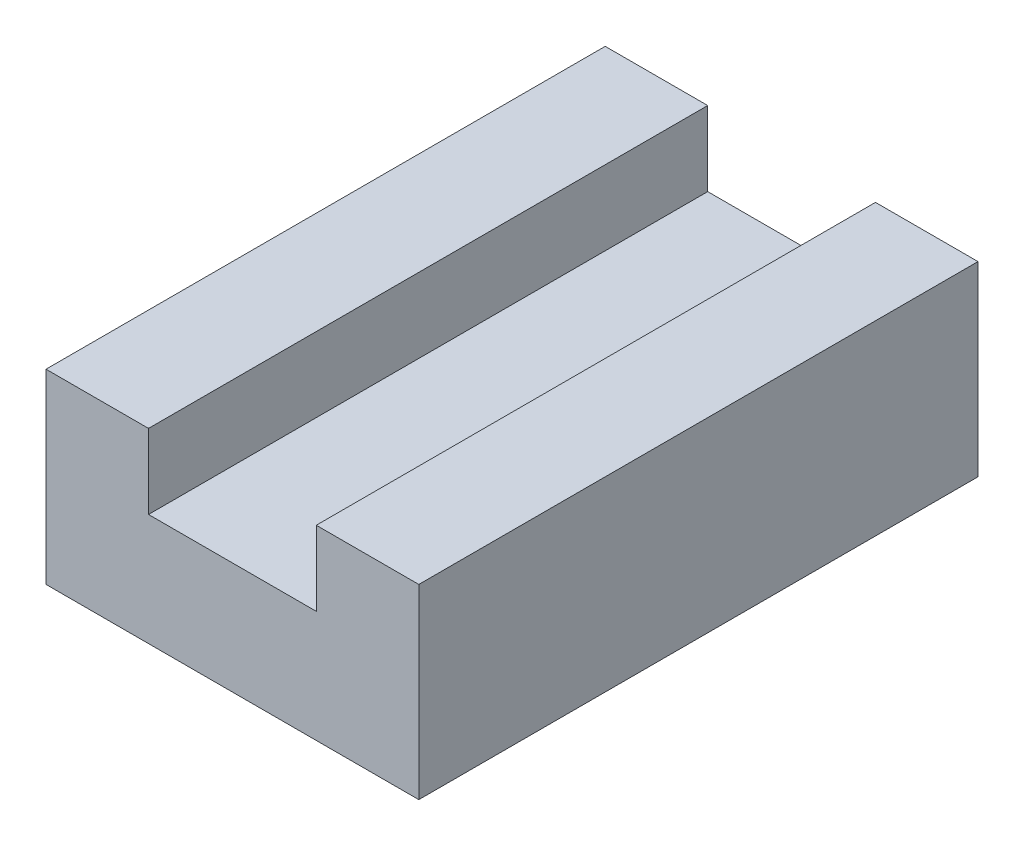
SolidWorks part; units mm, degrees
ref_plane "Front Plane" through (0, 0, 0) normal (0, 0, 1) x (1, 0, 0)
ref_plane "Top Plane" through (0, 0, 0) normal (0, 1, 0) x (1, 0, 0)
ref_plane "Right Plane" through (0, 0, 0) normal (1, 0, 0) x (0, 0, -1)
sketch "Sketch1" plane through (0, 0, 0) normal (0, 1, 0) x (1, 0, 0)
  line L1 (0, 0) -> (20, 0)
  line L2 (0, 0) -> (0, 30)
  line L3 (0, 30) -> (20, 30)
  line L4 (20, 0) -> (20, 30)
  dimension "D1" = 20
  dimension "D2" = 30
extrude "Boss-Extrude1" add sketch "Sketch1" along normal blind 10
sketch "Sketch2" plane through (0, 0, 0) normal (0, 0, 1) x (1, 0, 0)
  line L0 (0, 10) -> (20, 10) construction
  line L1 (5.5, 10) -> (14.5, 10)
  line L2 (5.5, 10) -> (5.5, 6)
  line L3 (5.5, 6) -> (14.5, 6)
  line L4 (14.5, 10) -> (14.5, 6)
  line L5 (10, 10) -> (10, 0) construction
  line L6 (0, 0) -> (20, 0) construction
  point P10 (0, 0)
  dimension "D1" = 9
  dimension "D2" = 4
extrude "Cut-Extrude1" cut sketch "Sketch2" against normal through all
sketch "Sketch3" plane through (0, 0, 0) normal (0, -1, 0) x (1, 0, 0)
  line L0 (10, -30) -> (10, 0) construction
  line L1 (20, -30) -> (0, -30) construction
  line L2 (0, 0) -> (20, 0) construction
  circle A0 centre (2.5, -19.6821) radius 1.5
  circle A1 centre (17.5, -19.6821) radius 1.5
  circle A2 centre (17.5, -9.6821) radius 1.5
  circle A3 centre (2.5, -9.6821) radius 1.5
  point P8 (0, 0)
  dimension "D1" = 3
  dimension "D2" = 3
  dimension "D3" = 3
  dimension "D4" = 3
  dimension "D5" = 10
  dimension "D6" = 15
extrude "Cut-Extrude2" cut sketch "Sketch3" against normal blind 5
